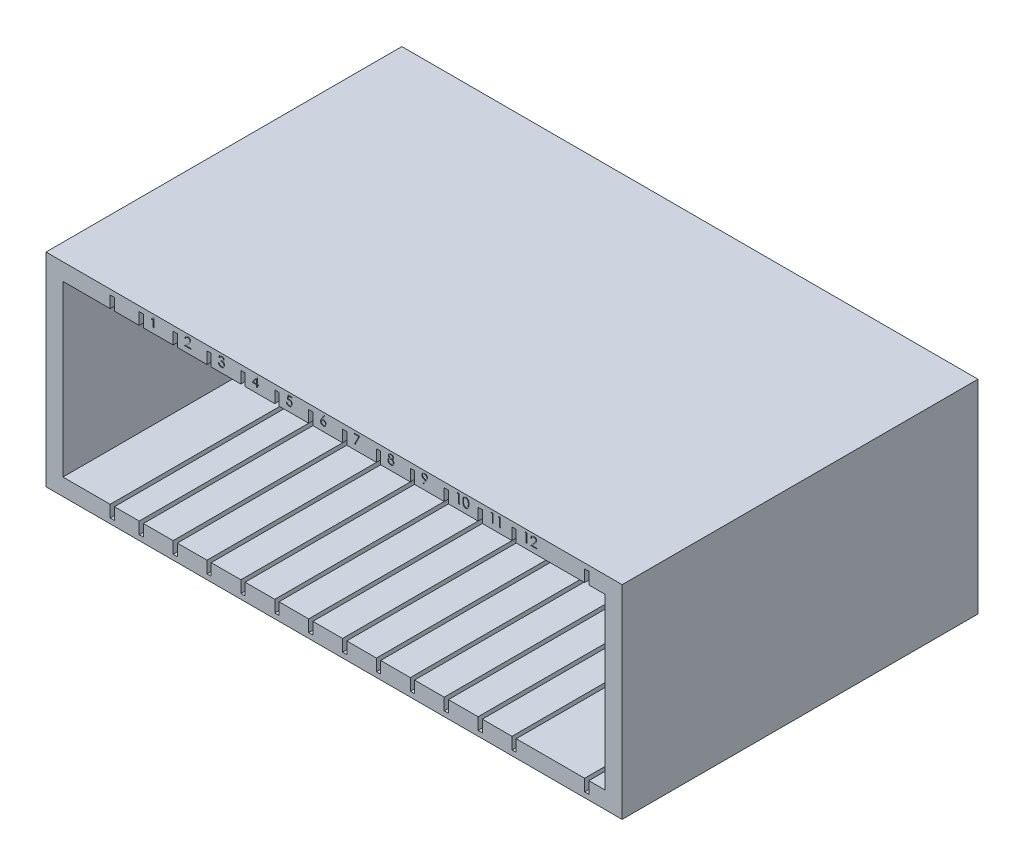
SolidWorks part; units mm, degrees
material "ABS"
ref_plane "Front Plane" through (0, 0, 0) normal (0, 0, 1) x (1, 0, 0)
ref_plane "Top Plane" through (0, 0, 0) normal (0, 1, 0) x (1, 0, 0)
ref_plane "Right Plane" through (0, 0, 0) normal (1, 0, 0) x (0, 0, -1)
sketch "Sketch1" plane through (0, 0, 0) normal (0, 0, 1) x (1, 0, 0)
  line L1 (107.95, -38.1) -> (-107.95, -38.1)
  line L2 (107.95, -38.1) -> (107.95, 38.1)
  line L3 (107.95, 38.1) -> (-107.95, 38.1)
  line L4 (-107.95, -38.1) -> (-107.95, 38.1)
  line L5 (107.95, -38.1) -> (-107.95, 38.1) construction
  line L6 (107.95, 38.1) -> (-107.95, -38.1) construction
  point P0 (0, 0)
  dimension "D1" = 215.9
  dimension "D2" = 76.2
extrude "Boss-Extrude1" add sketch "Sketch1" along normal blind 133.35
shell "Shell1" thickness 6.35 removed face at (0, 0, 133.35)
sketch "Sketch2" plane through (0, 0, 133.35) normal (0, 0, 1) x (1, 0, 0)
  line L0 (-101.6, 31.75) -> (-101.6, -31.75) construction
  line L1 (-73.025, 36.195) -> (-71.4375, 36.195)
  line L2 (-73.025, 36.195) -> (-73.025, -36.195)
  line L3 (-73.025, -36.195) -> (-71.4375, -36.195)
  line L4 (-71.4375, 36.195) -> (-71.4375, -36.195)
  line L5 (-73.025, 36.195) -> (-71.4375, -36.195) construction
  line L6 (-73.025, -36.195) -> (-71.4375, 36.195) construction
  point P0 (-72.2312, 0)
  dimension "D1" = 72.39
  dimension "D2" = 1.5875
  dimension "D3" = 28.575
extrude "Cut-Extrude1" cut sketch "Sketch2" against normal up to surface (127 mm away) up to face at (0, 0, 6.35)
pattern_linear "LPattern1" count 12 spacing 12.7 along (1, 0, 0) of "Cut-Extrude1"
sketch "Sketch3" plane through (0, 0, 133.35) normal (0, 0, 1) x (1, 0, 0)
  line L1 (93.8936, 36.195) -> (95.4811, 36.195)
  line L2 (93.8936, 36.195) -> (93.8936, -36.195)
  line L3 (93.8936, -36.195) -> (95.4811, -36.195)
  line L4 (95.4811, 36.195) -> (95.4811, -36.195)
  line L5 (93.8936, 36.195) -> (95.4811, -36.195) construction
  line L6 (93.8936, -36.195) -> (95.4811, 36.195) construction
  line L8 (92.075, -984.996) -> (92.075, 49015.004) construction
  line L10 (68.2625, 36.195) -> (66.675, 36.195) construction
  line L11 (66.675, -36.195) -> (68.2625, -36.195) construction
  point P0 (94.6874, 0)
  dimension "D1" = 1.8186
  dimension "D2" = 25.4
extrude "Cut-Extrude2" cut sketch "Sketch3" against normal up to surface (127 mm away)
sketch "Sketch4" plane through (0, 0, 133.35) normal (0, 0, 1) x (1, 0, 0)
  line L0 (-73.025, 31.75) -> (-73.025, 36.195) construction
  line L1 (-83.9064, 36.195) -> (-82.3189, 36.195)
  line L2 (-83.9064, 36.195) -> (-83.9064, -36.195)
  line L3 (-83.9064, -36.195) -> (-82.3189, -36.195)
  line L4 (-82.3189, 36.195) -> (-82.3189, -36.195)
  line L5 (-83.9064, 36.195) -> (-82.3189, -36.195) construction
  line L6 (-83.9064, -36.195) -> (-82.3189, 36.195) construction
  line L7 (-73.025, 36.195) -> (-71.4375, 36.195) construction
  line L8 (-71.4375, -36.195) -> (-73.025, -36.195) construction
  point P0 (-83.1126, 0)
  point P5 (-77.7532, 34.991)
  point P6 (-81.7565, -34.3557)
  dimension "D1" = 10.8814
extrude "Cut-Extrude3" cut sketch "Sketch4" against normal up to surface (127 mm away)
sketch "Sketch5" plane through (0, 0, 133.35) normal (0, 0, 1) x (1, 0, 0)
  line L0 (-68.8975, 33.655) -> (-56.1975, 33.655) construction
  line L1 (-56.1975, 33.655) -> (-43.4975, 33.655) construction
  line L2 (-43.4975, 33.655) -> (-30.7975, 33.655) construction
  line L3 (-30.7975, 33.655) -> (-18.0975, 33.655) construction
  line L4 (-18.0975, 33.655) -> (-5.3975, 33.655) construction
  line L5 (-5.3975, 33.655) -> (7.3025, 33.655) construction
  line L6 (7.3025, 33.655) -> (20.0025, 33.655) construction
  line L7 (20.0025, 33.655) -> (32.7025, 33.655) construction
  line L8 (32.7025, 33.655) -> (45.4025, 33.655) construction
  line L9 (45.4025, 33.655) -> (58.1025, 33.655) construction
  line L10 (58.1025, 33.655) -> (70.8025, 33.655) construction
  line L11 (-60.325, 31.75) -> (-71.4375, 31.75) construction
  line L12 (-71.4375, 36.195) -> (-71.4375, 31.75) construction
  text T0 "1" font "Arial Narrow" height 3.5
  text T1 "2"
  text T2 "3"
  text T3 "4"
  text T4 "5"
  text T5 "6"
  text T6 "7"
  text T7 "8"
  text T8 "9"
  text T9 "10"
  text T10 "11"
  text T11 "12"
  dimension "D1" = 12.7
  dimension "D2" = 1.905
  dimension "D3" = 2.54
extrude "Cut-Extrude4" cut sketch "Sketch5" against normal blind 0.254
